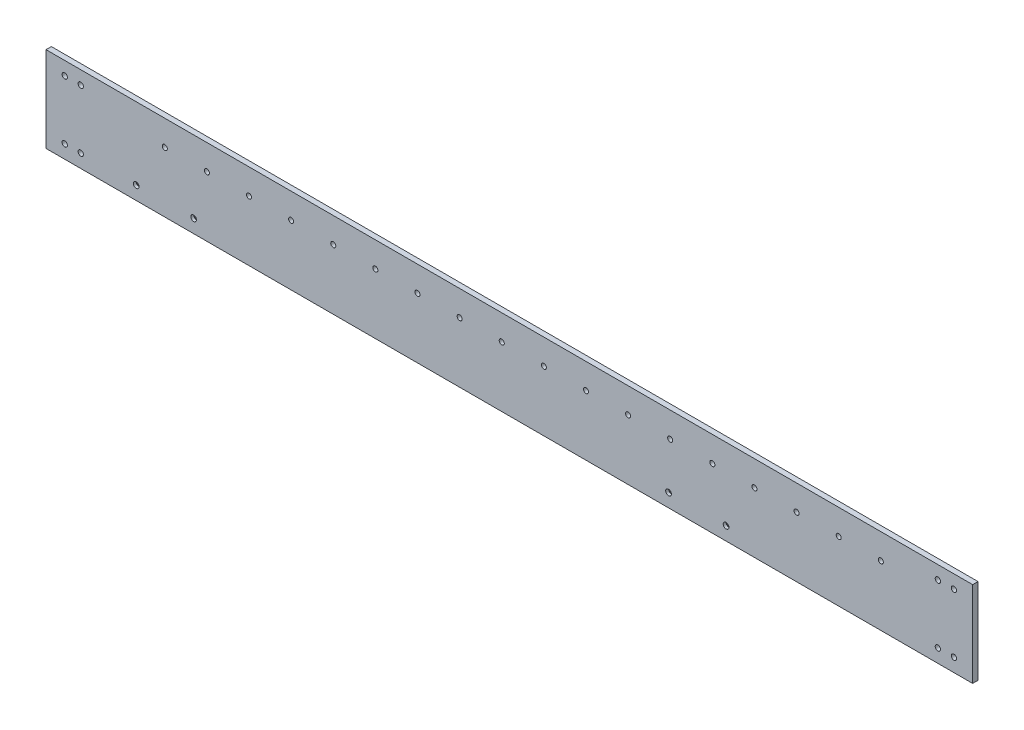
SolidWorks part; units mm, degrees
ref_plane "Front Plane" through (0, 0, 0) normal (0, 0, 1) x (1, 0, 0)
ref_plane "Top Plane" through (0, 0, 0) normal (0, 1, 0) x (1, 0, 0)
ref_plane "Right Plane" through (0, 0, 0) normal (1, 0, 0) x (0, 0, -1)
sketch "Sketch1" plane through (0, 0, 0) normal (1, 0, 0) x (0, 0, -1)
  line L0 (0, 0) -> (-3.175, 0)
  line L3 (-3.175, 0) -> (-3.175, 50.8)
  line L4 (-3.175, 50.8) -> (0, 50.8)
  line L5 (0, 50.8) -> (0, 0)
  dimension "LHeight" = 50.8
  dimension "LMaterialThickness" = 3.175
extrude "Boss-Extrude1" add sketch "Sketch1" along normal blind 550
sketch "LeftSideHoles-Sketch4" plane through (0, 0, 3.175) normal (0, 0, 1) x (1, 0, 0)
  line L0 (550, 50.8) -> (550, 0) construction
  line L1 (0, 50.8) -> (0, 0) construction
  line L2 (550, 50.8) -> (550, 0) construction
  line L3 (550, 50.8) -> (0, 50.8) construction
  line L4 (550, 0) -> (0, 0) construction
  line L5 (550, 50.8) -> (0, 50.8) construction
  line L6 (0, 50.8) -> (0, 0) construction
  circle A1 centre (11.1125, 42.8625) radius 1.5875
  circle A3 centre (529.3625, 42.8625) radius 1.5875
  circle A4 centre (20.6375, 42.8625) radius 1.5875
  circle A5 centre (538.8875, 42.8625) radius 1.5875
  circle A6 centre (11.1125, 7.9375) radius 1.5875
  circle A7 centre (20.6375, 7.9375) radius 1.5875
  circle A8 centre (529.3625, 7.9375) radius 1.5875
  circle A9 centre (538.8875, 7.9375) radius 1.5875
  circle A10 centre (495.5, 35.8) radius 1.5
  circle A11 centre (470.5, 35.8) radius 1.5
  circle A12 centre (445.5, 35.8) radius 1.5
  circle A13 centre (420.5, 35.8) radius 1.5
  circle A14 centre (395.5, 35.8) radius 1.5
  circle A15 centre (370.5, 35.8) radius 1.5
  circle A16 centre (345.5, 35.8) radius 1.5
  circle A17 centre (320.5, 35.8) radius 1.5
  circle A18 centre (295.5, 35.8) radius 1.5
  circle A19 centre (270.5, 35.8) radius 1.5
  circle A20 centre (245.5, 35.8) radius 1.5
  circle A21 centre (220.5, 35.8) radius 1.5
  circle A22 centre (195.5, 35.8) radius 1.5
  circle A23 centre (170.5, 35.8) radius 1.5
  circle A24 centre (145.5, 35.8) radius 1.5
  circle A25 centre (120.5, 35.8) radius 1.5
  circle A26 centre (95.5, 35.8) radius 1.5
  circle A27 centre (70.5, 35.8) radius 1.5
  circle A28 centre (53.5125, 7.9375) radius 1.5875
  circle A31 centre (369.5125, 7.9375) radius 1.5875
  circle A33 centre (87.6375, 7.9375) radius 1.5875
  circle A35 centre (403.6375, 7.9375) radius 1.5875
  dimension "D2" = 3.175
  dimension "D10" = 3
  dimension "D14" = 3.175
  dimension "D4" = 7.9375
  dimension "D1" = 11.1125
  dimension "D6" = 20.6375
  dimension "D3" = 11.1125
  dimension "D5" = 20.6375
  dimension "D7" = 7.9375
  dimension "D8" = 54.5
  dimension "D12" = 25
  dimension "D13" = 7.9375
  dimension "D15" = 53.5125
  dimension "D17" = 316
  dimension "D20" = 34.125
  dimension "D16" = 34.125
  dimension "D9" = 15
  dimension "D11" = 18
extrude "LeftSideHoles-Cut-Extrude3" cut sketch "LeftSideHoles-Sketch4" against normal through all
sketch "Sketch2" plane through (0, 0, 0) normal (0, 0, -1) x (-1, 0, 0)
  point P0 (-403.6375, 7.9375)
  point P3 (-369.5125, 7.9375)
  point P6 (-87.6375, 7.9375)
  point P9 (-53.5125, 7.9375)
hole_wizard "CSK for M3 Flat Head Machine Screw1" positions "Sketch2" profile "Sketch3" countersink size "M3" standard "ANSI Metric" end condition through all
sketch "Sketch3" plane through (403.6375, 7.9375, 0) normal (1, 0, 0) x (0, 1, 0)
  line L0 (0, 0) -> (0, 3.175)
  line L1 (0, 3.175) -> (1.7, 3.175)
  line L2 (1.7, 3.175) -> (1.7, 1.45)
  line L3 (1.7, 1.45) -> (3.15, 0)
  line L5 (3.15, 0) -> (0, 0)
  line L6 (-1.7, 1.45) -> (-3.15, 0) construction
  line L11 (0, -6.35) -> (0, 107.95) construction
  dimension "Thru Hole Dia." = 3.4
  dimension "Thru Hole Depth" = 3.175
  dimension "Near C'Sink Dia." = 6.3
  dimension "Near C'Sink Angle" = 90
equation "\"RailThickness\"= .125in'Spec"
equation "\"SideRailHoleY1FromEdge\"= \"HoleOffsetFromEdge\""
equation "\"SideRailHoleX1FromSide\"= \"HoleOffsetFromSide\""
equation "\"MidSideRailLength\"= \"SideRailLength\""
equation "\"VSWidth\"= 1.25in'Spec"
equation "\"HoleOffsetFromEdge\"= \"RailThickness\" * 2.5"
equation "\"HoleOffsetFromSide\"= \"RailThickness\" * 3.5"
equation "\"SideRailHoleX2FromSide\"= \"VSWidth\" - \"HoleOffsetFromEdge\" - \"RailThickness\"'Equals 20.6375"
equation "\"FasteningHoleDiameter\"= .125in"
equation "\"D2@LeftSideHoles-Sketch4\" = \"FasteningHoleDiameter\""
equation "\"LHeight@Sketch1\"=\"MidLeftOrRightSideRailHeight\""
equation "\"LMaterialThickness@Sketch1\"=\"RailThickness\""
equation "\"D1@Boss-Extrude1\"=\"MidSideRailLength\""
equation "\"D4@LeftSideHoles-Sketch4\" = \"SideRailHoleY1FromEdge\""
equation "\"D1@LeftSideHoles-Sketch4\"=\"SideRailHoleX1FromSide\""
equation "\"D6@LeftSideHoles-Sketch4\"=\"SideRailHoleX2FromSide\" "
equation "\"D3@LeftSideHoles-Sketch4\"=\"SideRailHoleX1FromSide\" "
equation "\"D5@LeftSideHoles-Sketch4\"=\"SideRailHoleX2FromSide\" "
equation "\"D7@LeftSideHoles-Sketch4\"=\"HoleOffsetFromEdge\""
equation "\"LinearRailXMountHole\"= \"StepperWidth\" + \"LinearRailFirstHoleOffsetFromEdge\""
equation "\"D8@LeftSideHoles-Sketch4\"=\"LinearRailXMountHole\""
equation "\"LinearRailHoleDistance\"= 25mm'Spec"
equation "\"D12@LeftSideHoles-Sketch4\"=\"LinearRailHoleDistance\""
equation "\"LinearRailFirstHoleOffsetFromEdge\"= 12.5mm'Spec"
equation "\"SideRailLength\"= 550mm"
equation "\"MidLeftOrRightSideRailHeight\"= 2.0in"
equation "\"StepperWidth\"= 42mm'Spec"
equation "\"StepperHolePadSize\"= \"StepperHoleDiameter\""
equation "\"MidRailRodStabilizerMountingHoleOffsetFromEdge\"= \"HoleOffsetFromEdge\""
equation "\"D13@LeftSideHoles-Sketch4\"=\"MidRailRodStabilizerMountingHoleOffsetFromEdge\""
equation "\"D14@LeftSideHoles-Sketch4\"=\"FasteningHoleDiameter\""
equation "\"DistanceFromBedFrontToFirstLeftStepperHole\"= \"LeadScrewNutPadSize\" + 10mm'Equals 34"
equation "\"BeltTensionerDepth\"= \"BeltTensionerBackWallThickness\" + \"BeltTensionerInnerDepth\"'Equals 23.4"
equation "\"20TGT2PulleyDiameter\"= 17.9mm'Spec"
equation "\"BeltTensionerSpaceBetweenPulleyAndWall\"= 1.5mm"
equation "\"BeltTensionerBackWallThickness\"= 4mm"
equation "\"BeltTensionerInnerDepth\"= \"20TGT2PulleyDiameter\" + \"BeltTensionerSpaceBetweenPulleyAndWall\""
equation "\"DistanceFromFrontSideToBedFront\"= \"RailThickness\" + \"BeltTensionerDepth\" + 10mm'Equals 36.575"
equation "\"DistanceFromFrontSideToFirstLeftStepperHole\"= \"DistanceFromFrontSideToBedFront\" + \"DistanceFromBedFrontToFirstLeftStepperHole\"'Equals 70.575"
equation "\"DistanceBetweenFrontToBackStepperHoles\"= \"BedLength\" - \"DistanceFromBedFrontToFirstLeftStepperHole\"'Equals 316"
equation "\"BedLength\"= \"BedInnerSquareLength\" + \"BedLWidth\" * 2 + \"BedIncreasedByLength\"'Equals 350"
equation "\"BedThirdSize\"= 70mm"
equation "\"BedInnerSquareWidth\"= \"BedThirdSize\" * 3'Equals 210"
equation "\"BedLWidth\"= \"BedThirdSize\"'Equals 70"
equation "\"BedIncreasedByLength\"= 0mm"
equation "\"BedInnerSquareLength\"= \"BedInnerSquareWidth\""
equation "\"DistanceFromFrontSideToFirstLeftRodStabilizerMountingHole\"= \"DistanceFromFrontSideToFirstLeftStepperHole\" - \"DistanceFromStepperHoleToRodStabilizerMountingHole\"'Equals 53.5125"
equation "\"D15@LeftSideHoles-Sketch4\"=\"DistanceFromFrontSideToFirstLeftRodStabilizerMountingHole\""
equation "\"D17@LeftSideHoles-Sketch4\"=\"DistanceBetweenFrontToBackStepperHoles\""
equation "\"LeadScrewNutMountingHoleFlangeDiameter\"= 22mm'Spec"
equation "\"LeadScrewNutPadSize\"= \"LeadScrewNutMountingHoleFlangeDiameter\" + 2mm'Equals 24"
equation "\"D20@LeftSideHoles-Sketch4\"=\"RodStabilizerLength\" - \"HoleOffsetFromEdge\" * 2"
equation "\"DistanceFromStepperHoleToRodStabilizerMountingHole\"= \"RodStabilizerLength\" / 2 - \"HoleOffsetFromEdge\"'Equals 17.0625"
equation "\"RodStabilizerLength\"= 50mm"
equation "\"D16@LeftSideHoles-Sketch4\"=\"RodStabilizerLength\" - \"HoleOffsetFromEdge\" * 2"
equation "\"LinearRailWidth\"= 12mm'Spec"
equation "\"MidSideRailVerticalOffset\"= \"LinearRailWidth\" + 3mm'Allows space for RodStabilizer to attach to bottom of MidSideRail"
equation "\"D9@LeftSideHoles-Sketch4\"=\"MidSideRailVerticalOffset\""
